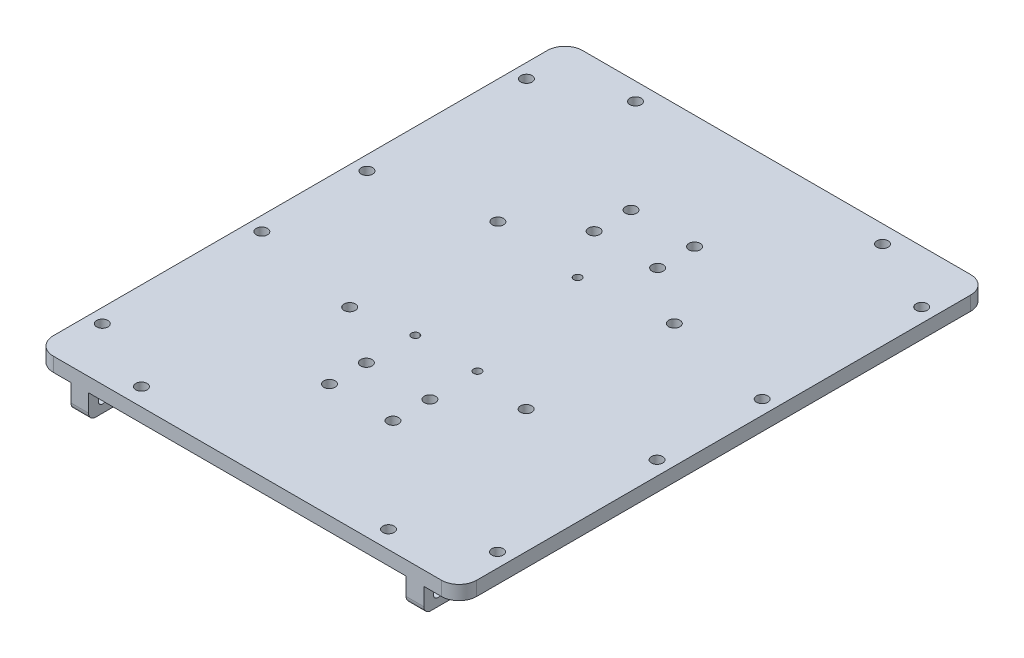
SolidWorks part; units mm, degrees
material "自定义塑料"
ref_plane "前视基准面" through (0, 0, 0) normal (0, 0, 1) x (1, 0, 0)
ref_plane "上视基准面" through (0, 0, 0) normal (0, 1, 0) x (1, 0, 0)
ref_plane "右视基准面" through (0, 0, 0) normal (1, 0, 0) x (0, 0, -1)
sketch "草图1" plane through (0, 0, 0) normal (0, 1, 0) x (1, 0, 0)
  line L0 (0, 0) -> (-20.2314, 0) construction
  line L1 (-60, 75) -> (60, 75)
  line L2 (-60, 75) -> (-60, -75)
  line L3 (-60, -75) -> (60, -75)
  line L4 (60, 75) -> (60, -75)
  line L5 (-60, 75) -> (60, -75) construction
  line L6 (-60, -75) -> (60, 75) construction
  line L7 (0, 0) -> (0, 21.0425) construction
  line L8 (-60, 37.5) -> (-53.3899, 37.5) construction
  circle A0 centre (-56, 60.1) radius 1.6
  circle A1 centre (-56, 14.9) radius 1.6
  circle A2 centre (-9, 42.73) radius 1.6
  circle A3 centre (-9, 32.27) radius 1.6
  circle A4 centre (-56, -14.9) radius 1.6
  circle A5 centre (-9, -32.27) radius 1.6
  circle A6 centre (-9, -42.73) radius 1.6
  circle A7 centre (-56, -60.1) radius 1.6
  circle A8 centre (56, -60.1) radius 1.6
  circle A9 centre (9, -42.73) radius 1.6
  circle A10 centre (9, -32.27) radius 1.6
  circle A11 centre (56, -14.9) radius 1.6
  circle A12 centre (56, 14.9) radius 1.6
  circle A13 centre (9, 32.27) radius 1.6
  circle A14 centre (9, 42.73) radius 1.6
  circle A15 centre (56, 60.1) radius 1.6
  circle A16 centre (0, 18.6) radius 1.1
  circle A17 centre (8.8, -18.6) radius 1.1
  circle A18 centre (-8.8, -18.6) radius 1.1
  circle A19 centre (-25, 21) radius 1.6
  circle A20 centre (25, 21) radius 1.6
  circle A21 centre (25, -21) radius 1.6
  circle A22 centre (-25, -21) radius 1.6
  circle A23 centre (35, 70) radius 1.6
  circle A24 centre (-35, 70) radius 1.6
  circle A25 centre (-35, -70) radius 1.6
  circle A26 centre (35, -70) radius 1.6
  point P0 (0, 0)
  dimension "D4" = 3.2
  dimension "D9" = 2.2
  dimension "D15" = 3.2
  dimension "D16" = 3.2
  dimension "D17" = 70
  dimension "D18" = 140
  dimension "D1" = 120
  dimension "D2" = 150
  dimension "D3" = 37.5
  dimension "D5" = 45.2
  dimension "D6" = 4
  dimension "D7" = 10.46
  dimension "D8" = 47
  dimension "D10" = 18.6
  dimension "D11" = 18.6
  dimension "D12" = 8.8
  dimension "D13" = 50
  dimension "D14" = 42
extrude "凸台-拉伸1" add sketch "草图1" along normal blind 4
ref_plane "基准面1" through (-50, 0, 0) normal (-1, 0, 0) x (0, 0, 1)
sketch "草图2" plane through (-50, 0, 0) normal (-1, 0, 0) x (0, 0, 1)
  line L0 (45, 0) -> (75, 0)
  line L1 (-75, 0) -> (75, 0) construction
  line L2 (75, 0) -> (75, -7)
  line L4 (57.1244, -7) -> (45, 0)
  line L5 (75, 4) -> (75, 0) construction
  line L6 (0, 31.7776) -> (0, -46.127) construction
  line L9 (-72.6356, 0) -> (-75, 0)
  line L11 (57.1244, -7) -> (75, -7)
  line L14 (-57.1244, -7) -> (-75, -7)
  line L15 (-57.1244, -7) -> (-45, 0)
  line L16 (-75, 0) -> (-75, -7)
  line L17 (-45, 0) -> (-75, 0)
  circle A6 centre (71, -3.5) radius 1.25
  circle A7 centre (-71, -3.5) radius 1.25
  circle A10 centre (65, -3.5) radius 1.25
  circle A11 centre (59, -3.5) radius 1.25
  circle A12 centre (-65, -3.5) radius 1.25
  circle A13 centre (-59, -3.5) radius 1.25
  dimension "D1" = 7
  dimension "D2" = 2.5
  dimension "D6" = 3.5
  dimension "D7" = 4
  dimension "D8" = 3
  dimension "D3" = 90
  dimension "D4" = 30
  dimension "D5" = 30
extrude "凸台-拉伸2" add sketch "草图2" against normal blind 5 contours L4 L11 L2 L0 | L15 L17 L9 L16 L14 A7 region at (-50, -3.1761, 62.5609) region at (-50, -3.1761, -62.5609)
ref_plane "基准面2" through (0, 0, 0) normal (-1, 0, 0) x (0, 0, 1)
mirror "镜向1" about plane through (0, 0, 0) normal (-1, 0, 0) of "凸台-拉伸2"
fillet "圆角1" radius 5 4 edges at (-60, 2, -75) (60, 2, -75) (60, 2, 75) (-60, 2, 75)
fillet "圆角3" radius 2 12 edges at (-47.5, 0, 45) (-47.5, -7, 57.1244) (-47.5, -7, 75) (47.5, -7, 75) (47.5, -7, 57.1244) (47.5, 0, 45) (47.5, 0, -45) (-47.5, 0, -45) (47.5, -7, -75) (47.5, -7, -57.1244) (-47.5, -7, -57.1244) (-47.5, -7, -75)
